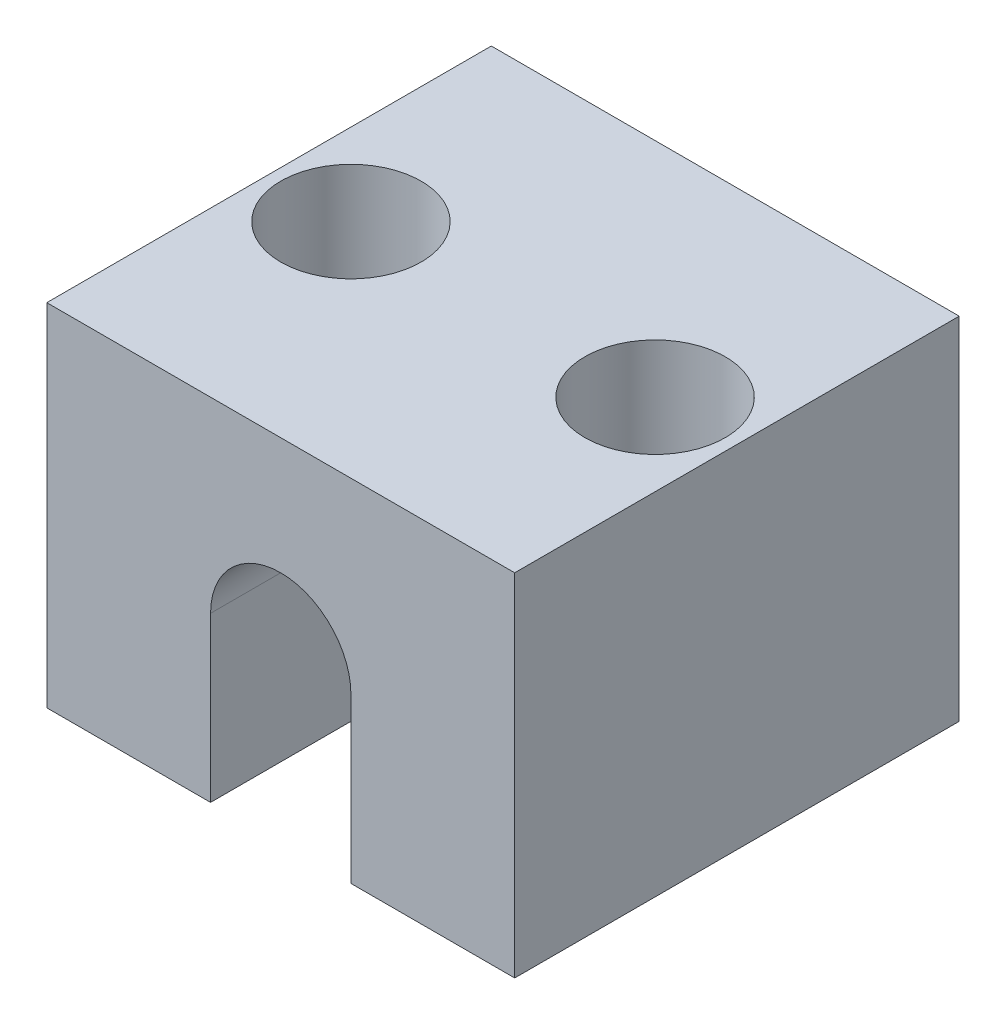
SolidWorks part; units mm, degrees
ref_plane "Front Plane" through (0, 0, 0) normal (0, 0, 1) x (1, 0, 0)
ref_plane "Top Plane" through (0, 0, 0) normal (0, 1, 0) x (1, 0, 0)
ref_plane "Right Plane" through (0, 0, 0) normal (1, 0, 0) x (0, 0, -1)
sketch "Sketch1" plane through (0, 0, 0) normal (0, 0, 1) x (1, 0, 0)
  line L0 (-10, 0) -> (-10, 15)
  line L1 (-10, 15) -> (10, 15)
  line L2 (-10, 0) -> (-3, 0)
  line L3 (3, 0) -> (10, 0)
  line L4 (10, 0) -> (10, 15)
  line L5 (3, 0) -> (3, 7)
  line L6 (-3, 0) -> (-3, 7)
  arc A2 (3, 7) -> (-3, 7) centre (0, 7) ccw
  point P3 (0, 0)
  point P12 (0, 0)
  dimension "D1" = 3
  dimension "D2" = 7
  dimension "D3" = 15
  dimension "D4" = 20
  dimension "D5" = 3
  dimension "D6" = 7
extrude "Boss-Extrude1" add sketch "Sketch1" along normal blind 19 contours L4 L1 L0 | L3 L2 region at (-9.75, 7.5, 0)
sketch "Sketch2" plane through (0, 15, 0) normal (0, 1, 0) x (1, 0, 0)
  line L0 (6.5, -19) -> (6.5, 0) construction
  line L1 (3, -19) -> (10, -19) construction
  line L2 (3, 0) -> (10, 0) construction
  line L3 (-6.5, 0) -> (-6.5, -19) construction
  line L4 (-10, 0) -> (-3, 0) construction
  line L5 (-10, -19) -> (-3, -19) construction
  circle A0 centre (-6.5, -9.5) radius 1.8
  circle A1 centre (6.5, -9.5) radius 1.8
  circle A2 centre (-6.5, -9.5) radius 3
  circle A3 centre (6.5, -9.5) radius 3
  dimension "D1" = 3.6
  dimension "D2" = 6
extrude "Cut-Extrude1" cut sketch "Sketch2" against normal through all contours A0 | A1 region at (-6.5, 15, 9.5) region at (6.5, 15, 9.5)
extrude "Cut-Extrude2" cut sketch "Sketch2<3>" against normal offset from surface (12 mm away) 3 contours A2 A0 | A3 A1 region at (-9.4151, 15, 9.5) region at (3.5849, 15, 9.5) up to face at (-6.5, 0, 11.3)
sketch "Sketch2<3>" plane through (0, 15, 0) normal (0, 1, 0) x (1, 0, 0) same geometry as "Sketch2"
